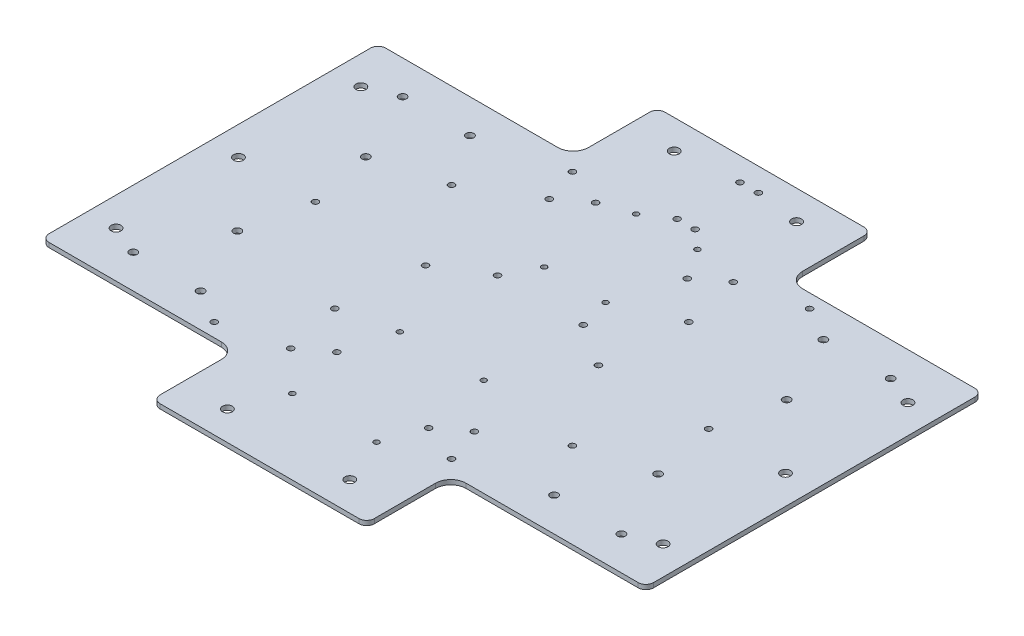
SolidWorks part; units mm, degrees
material "1060 Сплав"
ref_plane "Спереди" through (0, 0, 0) normal (0, 0, 1) x (1, 0, 0)
ref_plane "Сверху" through (0, 0, 0) normal (0, 1, 0) x (1, 0, 0)
ref_plane "Справа" through (0, 0, 0) normal (1, 0, 0) x (0, 0, -1)
sketch "Эскиз1" plane through (0, 0, 0) normal (0, 1, 0) x (1, 0, 0)
  line L1 (-65, -165) -> (65, -165)
  line L2 (-197.5, -105) -> (-197.5, 105)
  line L3 (-65, 165) -> (65, 165)
  line L4 (197.5, -105) -> (197.5, 105)
  line L5 (197.5, -105) -> (137.5, -105) construction
  line L6 (137.5, -110) -> (137.5, -66.2968) construction
  line L18 (-284.5497, 0) -> (284.3305, 0) construction
  line L19 (-160.9018, 110) -> (-134.9018, 110)
  line L39 (-70, 120) -> (-70, 160)
  line L40 (0, 262.7398) -> (0, -186.5795) construction
  line L41 (-192.5, 110) -> (-80, 110)
  line L43 (-192.5, -110) -> (-80, -110)
  line L44 (-70, -120) -> (-70, -160)
  line L45 (70, 120) -> (70, 160)
  line L46 (192.5, 110) -> (80, 110)
  line L47 (192.5, -110) -> (80, -110)
  line L48 (70, -120) -> (70, -160)
  line L54 (160.9018, -110) -> (134.9018, -110)
  line L60 (160.9018, 110) -> (134.9018, 110)
  line L65 (40, -146) -> (-40, -146) construction
  line L66 (-178.7687, -80) -> (-178.7687, 80) construction
  arc A0 (70, -120) -> (80, -110) centre (80, -120) cw
  arc A1 (70, 120) -> (80, 110) centre (80, 120) ccw
  arc A2 (-80, -110) -> (-70, -120) centre (-80, -120) cw
  arc A3 (-70, 120) -> (-80, 110) centre (-80, 120) cw
  arc A4 (192.5, -110) -> (197.5, -105) centre (192.5, -105) ccw
  arc A5 (70, -160) -> (65, -165) centre (65, -160) cw
  arc A6 (-70, -160) -> (-65, -165) centre (-65, -160) ccw
  arc A7 (-192.5, -110) -> (-197.5, -105) centre (-192.5, -105) cw
  arc A8 (-192.5, 110) -> (-197.5, 105) centre (-192.5, 105) ccw
  arc A9 (197.5, 105) -> (192.5, 110) centre (192.5, 105) ccw
  arc A10 (70, 160) -> (65, 165) centre (65, 160) ccw
  arc A11 (-70, 160) -> (-65, 165) centre (-65, 160) cw
  circle A12 centre (40, 146) radius 3.2
  circle A13 centre (40, -146) radius 3.2
  circle A14 centre (-40, -146) radius 3.2
  circle A15 centre (-40, 146) radius 3.2
  circle A16 centre (-178.7687, 80) radius 3.2
  circle A17 centre (-178.7687, -80) radius 3.2
  circle A18 centre (-178.7687, 0) radius 3.2
  circle A19 centre (178.7687, 80) radius 3.2
  circle A20 centre (178.7687, 0) radius 3.2
  circle A21 centre (178.7687, -80) radius 3.2
  circle A22 centre (137.5, -42) radius 2.5
  circle A23 centre (159.5, -88) radius 2.5
  circle A24 centre (115.5, -88) radius 2.5
  circle A25 centre (-159.5, -88) radius 2.5
  circle A26 centre (-137.5, -42) radius 2.5
  circle A27 centre (-115.5, -88) radius 2.5
  circle A28 centre (159.5, 88) radius 2.5
  circle A29 centre (137.5, 42) radius 2.5
  circle A30 centre (115.5, 88) radius 2.5
  circle A31 centre (-115.5, 88) radius 2.5
  circle A32 centre (-137.5, 42) radius 2.5
  circle A33 centre (-159.5, 88) radius 2.5
  point P0 (0, 0)
  point P3 (70, -110)
  point P17 (-147.9018, 110)
  point P18 (-147.9018, 110)
  point P46 (70, 110)
  point P52 (-70, -110)
  point P55 (-70, 110)
  point P56 (-147.9018, 0)
  point P59 (-178.7687, 0)
  point P62 (178.7687, 80)
  point P77 (197.5, -110)
  point P80 (70, -165)
  point P83 (-70, -165)
  point P86 (-197.5, -110)
  point P89 (-197.5, 110)
  point P92 (197.5, 110)
  point P95 (70, 165)
  point P98 (-70, 165)
  point P99 (178.7687, 0)
  point P100 (40, 146)
  point P101 (178.7687, -80)
  point P103 (-40, 146)
  dimension "D2" = 19
  dimension "D6" = 10
  dimension "D11" = 40
  dimension "D12" = 40
  dimension "D4" = 5
  dimension "D17" = 5
  dimension "D9" = 6.4
  dimension "D3" = 38
  dimension "D14" = 5
  dimension "D5" = 330
  dimension "D7" = 395
  dimension "D8" = 68
  dimension "D10" = 60
  dimension "D13" = 22
  dimension "D15" = 80
  dimension "D16" = 80
  dimension "D18" = 18.7313
  dimension "D19" = 19
  dimension "D20" = 140
extrude "Бобышка-Вытянуть1" add sketch "Эскиз1" along normal blind 3 separate body contours A11 L39 A3 L41 L43 A2 L44 A6 L1 A5 L48 A0 L47 L46 A1 L45 A10 L3 | L4 A9 L46 L47 A4 | L46 | L47 | L41 A8 L2 A7 L43 | L19 region at (0, 0, 0)
sketch "Эскиз2" plane through (0, 3, 0) normal (0, 1, 0) x (1, 0, 0)
  line L0 (197.5, 0) -> (-197.5, 0) construction
  line L1 (197.5, -105) -> (197.5, 105) construction
  line L2 (-197.5, -105) -> (-197.5, 105) construction
  line L3 (0, 165) -> (0, -165) construction
  line L4 (-65, 165) -> (65, 165) construction
  line L5 (-65, -165) -> (65, -165) construction
  line L6 (192.5, 110) -> (80, 110) construction
  circle A0 centre (128.5, 0) radius 2
  circle A1 centre (56.5, 0) radius 2
  circle A2 centre (93.5, 101) radius 2
  circle A3 centre (61.5, 54) radius 2
  circle A4 centre (49.5, 74) radius 2 construction
  circle A5 centre (53.5, 91.0922) radius 2
  circle A6 centre (36.503, 78.0468) radius 2
  circle A7 centre (28.6809, 17.8719) radius 2
  circle A8 centre (-27.3191, 17.8719) radius 2
  circle A9 centre (27.4963, -46.0223) radius 1.75
  circle A10 centre (93.5, -54.0533) radius 2
  circle A11 centre (61.5, -101.043) radius 2
  circle A12 centre (53.5, -78.0725) radius 2
  circle A13 centre (36.503, -90.9991) radius 2
  circle A14 centre (27.4963, -116.0332) radius 1.75
  circle A15 centre (-27.5526, -116.0332) radius 1.75
  circle A16 centre (-27.3191, -46) radius 1.75
  circle A17 centre (-53.6363, -90.9991) radius 2
  circle A18 centre (-36.4017, -78.0725) radius 2
  circle A19 centre (-93.5268, -101.043) radius 2
  circle A20 centre (-61.7277, -54.0533) radius 2
  circle A21 centre (-36.4017, 91.0922) radius 2
  circle A22 centre (-53.6363, 78.0468) radius 2
  circle A23 centre (-61.5417, 101) radius 2
  circle A24 centre (-93.5268, 54) radius 2
  circle A25 centre (-128.5, 0) radius 2
  circle A26 centre (-56.5, 0) radius 2
  circle A27 centre (-16.8323, 37.8725) radius 1.75
  circle A28 centre (-16.7978, 97.9276) radius 1.75
  circle A29 centre (23.276, 97.9276) radius 1.75
  circle A30 centre (23.276, 37.8725) radius 1.75
  circle A31 centre (-0.7596, 149.7308) radius 2
  circle A32 centre (11.1374, 149.8644) radius 2
  circle A33 centre (11.1374, 108.5129) radius 2
  circle A34 centre (-0.6279, 108.5129) radius 2
  point P15 (97.5, 105)
  point P19 (57.5, 50)
  point P24 (53.5, 101)
  point P25 (52.5, 81)
  dimension "D1" = 69
  dimension "D2" = 4
  dimension "D6" = 4
  dimension "D11" = 4
  dimension "D16" = 4
  dimension "D4" = 100
  dimension "D5" = 5
  dimension "D7" = 4
  dimension "D8" = 4
  dimension "D9" = 51
  dimension "D10" = 36
  dimension "D12" = 4
  dimension "D13" = 4
  dimension "D14" = 31
  dimension "D15" = 1
  dimension "D17" = 7
  dimension "D18" = 3
  dimension "D3" = 2
extrude "Вырез-Вытянуть1" cut sketch "Эскиз2" against normal blind 10
